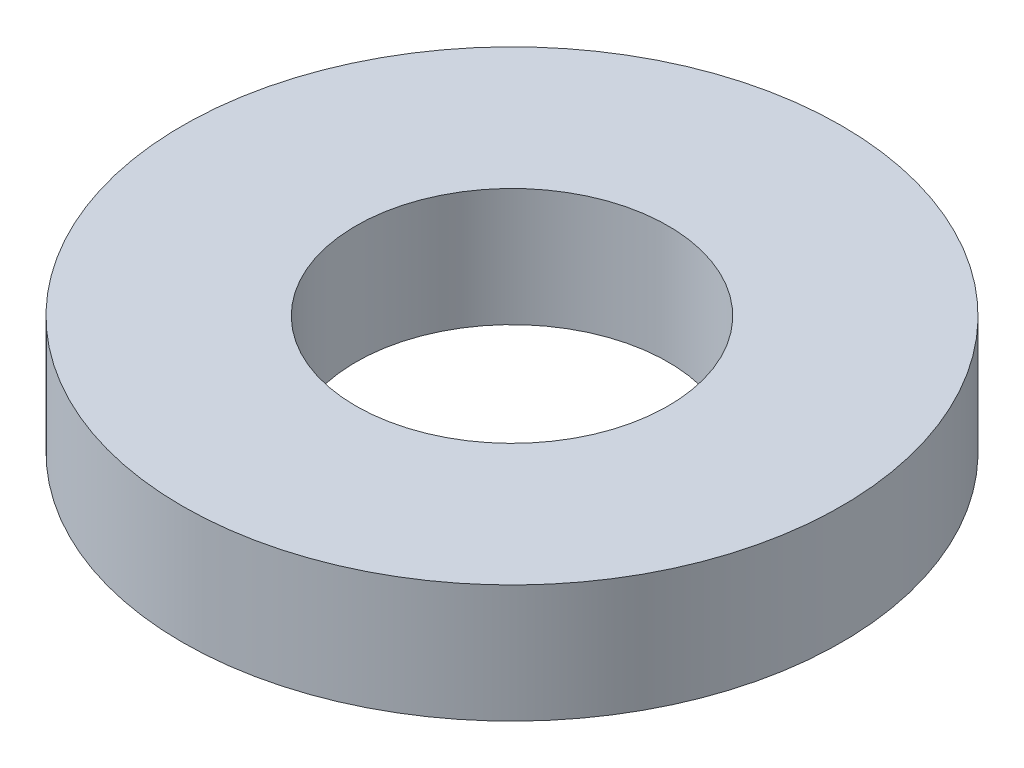
SolidWorks part; units mm, degrees
ref_plane "Front Plane" through (0, 0, 0) normal (0, 0, 1) x (1, 0, 0)
ref_plane "Top Plane" through (0, 0, 0) normal (0, 1, 0) x (1, 0, 0)
ref_plane "Right Plane" through (0, 0, 0) normal (1, 0, 0) x (0, 0, -1)
sketch "Sketch1" plane through (0, 0, 0) normal (0, 1, 0) x (1, 0, 0)
  circle A0 centre (0, 0) radius 47.5
  dimension "FLANGE_OD" = 95
extrude "Boss-Extrude1" add sketch "Sketch1" along normal blind 17
sketch "Sketch2" plane through (0, 0, 0) normal (0, 1, 0) x (1, 0, 0)
  circle A0 centre (0, 0) radius 22.5
  dimension "BORE_D" = 45
extrude "Cut-Extrude1" cut sketch "Sketch2" along normal through all
sketch "Sketch3" plane through (0, 17, 0) normal (0, 1, 0) x (1, 0, 0)
  circle A0 centre (0, 0) radius 13.6945 construction
  circle A1 centre (-13.6945, 0) radius 3.7919
  dimension "BOLT_D" = 7.5837
  dimension "BOLT_PCD" = 27.389
extrude "Cut-Extrude2" cut sketch "Sketch3" against normal blind 13.4776 rebuild error yes
pattern_circular "CirPattern1" count 4 over 360 rebuild error yes
